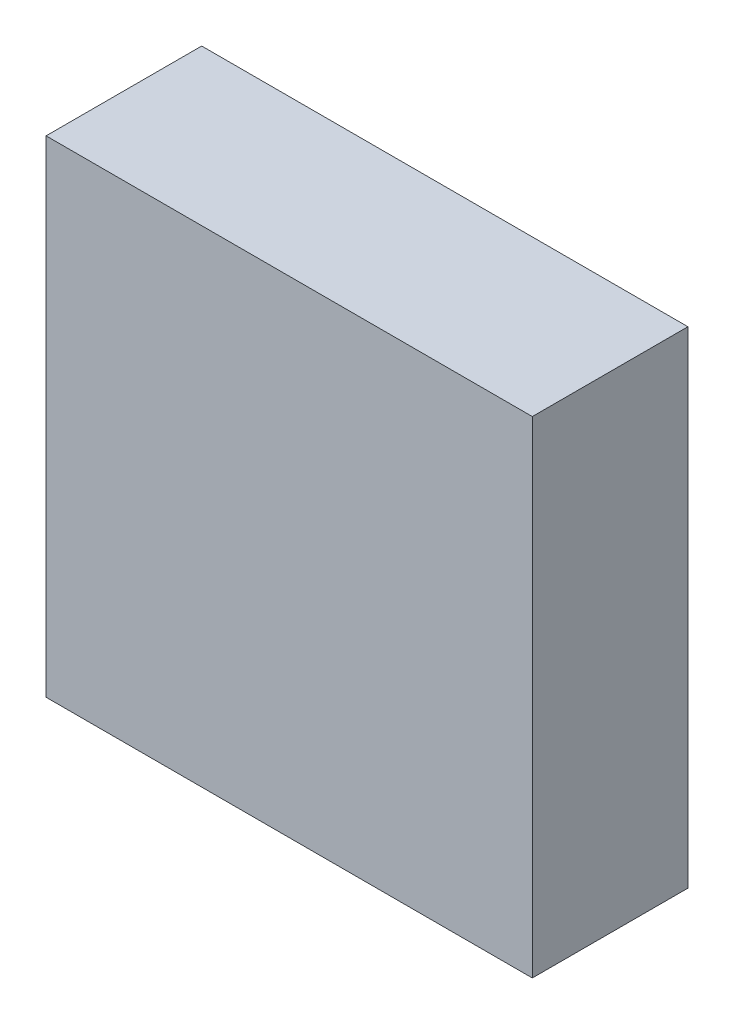
SolidWorks part; units mm, degrees
ref_plane "Front Plane" through (0, 0, 0) normal (0, 0, 1) x (1, 0, 0)
ref_plane "Top Plane" through (0, 0, 0) normal (0, 1, 0) x (1, 0, 0)
ref_plane "Right Plane" through (0, 0, 0) normal (1, 0, 0) x (0, 0, -1)
sketch "Sketch1" plane through (0, 0, 0) normal (0, 0, 1) x (1, 0, 0)
  line L1 (0, 0) -> (250, 0)
  line L2 (0, 0) -> (0, 250)
  line L3 (0, 250) -> (250, 250)
  line L4 (250, 0) -> (250, 250)
extrude "Boss-Extrude1" add sketch "Sketch1" along normal blind 80
